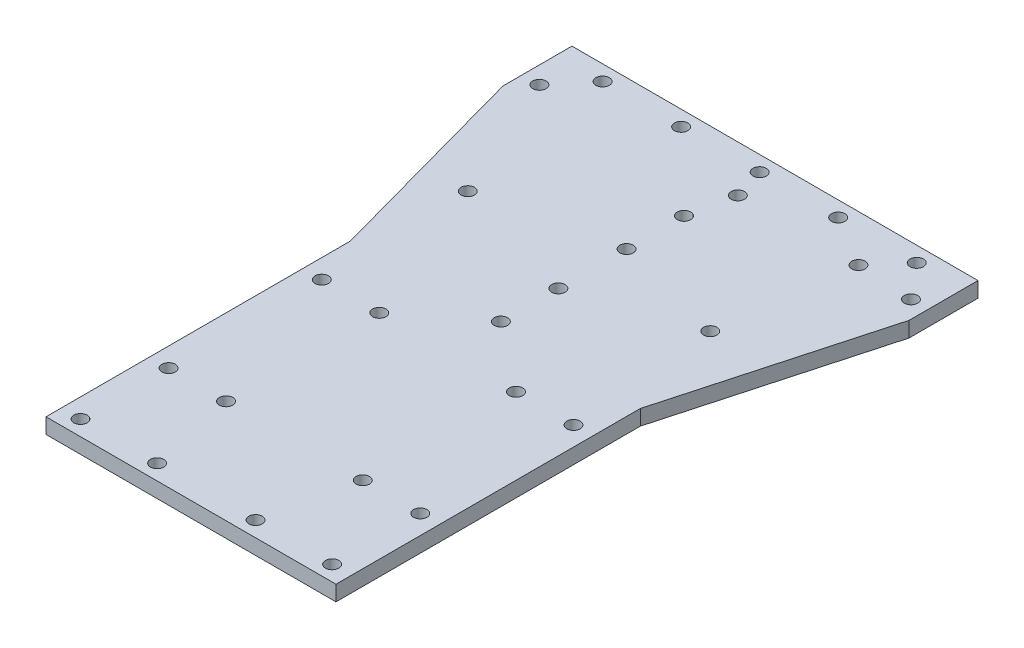
SolidWorks part; units mm, degrees
ref_plane "Front Plane" through (0, 0, 0) normal (0, 0, 1) x (1, 0, 0)
ref_plane "Top Plane" through (0, 0, 0) normal (0, 1, 0) x (1, 0, 0)
ref_plane "Right Plane" through (0, 0, 0) normal (1, 0, 0) x (0, 0, -1)
sketch "Sketch1" plane through (0, 0, 0) normal (0, 1, 0) x (1, 0, 0)
  line L1 (-37.85, 21.35) -> (37.85, 21.35)
  line L2 (-37.85, 21.35) -> (-37.85, -21.35)
  line L3 (-37.85, -21.35) -> (37.85, -21.35)
  line L4 (37.85, 21.35) -> (37.85, -21.35)
  line L5 (-37.85, 21.35) -> (37.85, -21.35) construction
  line L6 (-37.85, -21.35) -> (37.85, 21.35) construction
  circle A0 centre (2.4, 17.25) radius 1.75
  circle A1 centre (-33.8, -17.05) radius 1.75
  circle A2 centre (29.5, -17.05) radius 1.75
  circle A3 centre (33.9, 17.25) radius 1.75
  point P0 (0, 0)
  dimension "D9" = 3.5
  dimension "D1" = 75.7
  dimension "D2" = 42.7
  dimension "D3" = 4.1
  dimension "D4" = 4.3
  dimension "D5" = 4.05
  dimension "D6" = 8.35
  dimension "D7" = 3.95
  dimension "D8" = 40.25
extrude "Boss-Extrude1" add sketch "Sketch1" along normal blind 4
sketch "Sketch3" plane through (0, 4, 0) normal (0, 1, 0) x (1, 0, 0)
  line L0 (0, 0) -> (-31.55, 0) construction
  line L1 (-2.2, 0) -> (2.2, 0) construction
  line L2 (-31.55, 0) -> (-31.55, 14.5) construction
  line L3 (-31.55, 14.5) -> (27.25, 14.5) construction
  line L4 (27.25, 14.5) -> (27.25, -51.1) construction
  line L5 (27.25, -51.1) -> (-31.55, -51.1) construction
  line L6 (-31.55, -51.1) -> (-31.55, 0) construction
  line L7 (0, 14.5) -> (0, -51.1) construction
  line L8 (0, -2.2) -> (0, 2.2) construction
  line L9 (-31.55, -18.3) -> (27.25, -18.3) construction
  line L10 (-37.85, -21.35) -> (-37.85, -51.1)
  line L11 (37.85, -21.35) -> (37.85, -51.1)
  line L12 (37.85, -51.1) -> (-37.85, -51.1)
  line L13 (-37.85, -21.35) -> (37.85, -21.35)
  circle A0 centre (0, 5.6) radius 1.75
  circle A1 centre (0, -9.4) radius 1.75
  circle A2 centre (0, -27.2) radius 1.75
  circle A3 centre (0, -42.2) radius 1.75
  line M18 (-37.85, -21.35) -> (37.85, -21.35)
  dimension "D10" = 3.5
  dimension "D1" = 58.8
  dimension "D2" = 31.55
  dimension "D3" = 65.6
  dimension "D4" = 14.5
  dimension "D5" = 32.8
  dimension "D6" = 15
  dimension "D7" = 15
  dimension "D8" = 8.9
  dimension "D9" = 8.9
extrude "Boss-Extrude2" add sketch "Sketch3" against normal blind 4 contours L12 L11 L10 A3 A2 M18 region at (0, 4, 36.2381)
extrude "Cut-Extrude1" cut sketch "Sketch3<3>" against normal blind 4 contours A0 | A1
sketch "Sketch3<3>" plane through (0, 4, 0) normal (0, 1, 0) x (1, 0, 0) same geometry as "Sketch3"
sketch "Sketch4" plane through (0, 0, 0) normal (0, 1, 0) x (1, 0, 0)
  line L0 (-37.85, -51.1) -> (-37.85, -101.1) construction
  line L1 (-37.85, -101.1) -> (37.85, -101.1) construction
  line L2 (37.85, 21.35) -> (44, 21.35) construction
  line L3 (44, 21.35) -> (44, 29.35) construction
  line L4 (-37.85, 21.35) -> (-44, 21.35) construction
  line L6 (37.85, -51.1) -> (37.85, -101.1) construction
  line L7 (-44, 21.35) -> (-44, 29.35) construction
  line L8 (-44, 29.35) -> (44, 29.35) construction
  line L10 (-37.85, -51.1) -> (-37.85, -101.1)
  line L11 (-37.85, -101.1) -> (37.85, -101.1)
  line L12 (37.85, -101.1) -> (37.85, -51.1)
  line L13 (37.85, -51.1) -> (-37.85, -51.1)
  line L14 (-37.85, 21.35) -> (-44, 21.35)
  line L15 (-44, 21.35) -> (-44, 29.35)
  line L16 (-44, 29.35) -> (44, 29.35)
  line L17 (44, 29.35) -> (44, 21.35)
  line L18 (44, 21.35) -> (37.85, 21.35)
  line L19 (37.85, 21.35) -> (-37.85, 21.35)
  line L20 (0, -2.2) -> (0, 2.2) construction
  circle A0 centre (-32.85, -56.1) radius 1.75
  circle A1 centre (-17.85, -56.1) radius 1.75
  circle A2 centre (-17.85, -96.1) radius 1.75
  circle A3 centre (-32.85, -96.1) radius 1.75
  circle A4 centre (32.85, -96.1) radius 1.75
  circle A5 centre (17.85, -96.1) radius 1.75
  circle A6 centre (17.85, -56.1) radius 1.75
  circle A7 centre (32.85, -56.1) radius 1.75
  dimension "D5" = 3.5
  dimension "D1" = 88
  dimension "D2" = 8
  dimension "D3" = 50
  dimension "D4" = 6.15
  dimension "D6" = 15
  dimension "D7" = 5
  dimension "D8" = 5
  dimension "D9" = 5
extrude "Boss-Extrude3" add sketch "Sketch4" along normal blind 4
sketch "Sketch6" plane through (0, 4, 0) normal (0, 1, 0) x (1, 0, 0)
  line L0 (-44, 25.35) -> (44, 25.35) construction
  line L1 (-44, 29.35) -> (-44, 21.35) construction
  line L2 (44, 21.35) -> (44, 29.35) construction
  line L3 (-44, 29.35) -> (-53, 29.35)
  line L4 (-53, 29.35) -> (-53, 21.35)
  line L5 (-53, 21.35) -> (-44, 21.35)
  line L6 (44, 29.35) -> (53, 29.35)
  line L7 (53, 29.35) -> (53, 21.35)
  line L8 (53, 21.35) -> (44, 21.35)
  line L9 (44, 21.35) -> (44, 26.2514)
  line L10 (44, 29.35) -> (44, 26.2514)
  line L11 (-44, 21.35) -> (-44, 26.2514)
  line L12 (-44, 29.35) -> (-44, 26.2514)
  circle A0 centre (0, 25.35) radius 1.75
  circle A1 centre (20.5, 25.35) radius 1.75
  circle A2 centre (41, 25.35) radius 1.75
  circle A3 centre (-20.5, 25.35) radius 1.75
  circle A4 centre (-41, 25.35) radius 1.75
  point P29 (-44, 26.1589)
  point P30 (0, 0)
  point P31 (0, 0)
  point P34 (0, 0)
  point P35 (0, 0)
  point P36 (44, 26.0344)
  line M16 (44, 21.35) -> (44, 29.35)
  line M18 (-44, 29.35) -> (-44, 21.35)
  dimension "D5" = 3.5
  dimension "D1" = 20.5
  dimension "D2" = 20.5
  dimension "D3" = 20.5
  dimension "D4" = 20.5
  dimension "D6" = 12
  dimension "D7" = 12
extrude "Boss-Extrude4" add sketch "Sketch6" against normal blind 4 contours A4 L3 L4 L5 M18 | A2 L8 L7 L6 M16 region at (-48.5, 4, -25.35) region at (48.5, 4, -25.35)
extrude "Cut-Extrude2" cut sketch "Sketch6<3>" against normal through all contours A4 | A3 | A1 | A2 | A0
sketch "Sketch6<3>" plane through (0, 4, 0) normal (0, 1, 0) x (1, 0, 0) same geometry as "Sketch6"
sketch "Sketch7" plane through (0, 0, 0) normal (0, 1, 0) x (1, 0, 0)
  line L0 (-53, 21.35) -> (-53, 11.35)
  line L1 (-53, 11.35) -> (-37.85, 11.35)
  line L2 (-37.85, 21.35) -> (-37.85, -101.1) construction
  line L3 (-37.85, 11.35) -> (-37.85, 21.35)
  line L4 (-37.85, 21.35) -> (-53, 21.35)
  line L5 (53, 21.35) -> (53, 11.35)
  line L6 (53, 11.35) -> (37.85, 11.35)
  line L7 (37.85, -101.1) -> (37.85, 21.35) construction
  line L8 (37.85, 11.35) -> (37.85, 21.35)
  line L9 (37.85, 21.35) -> (53, 21.35)
  circle A0 centre (-48.5, 16.35) radius 1.75
  circle A1 centre (48.5, 16.35) radius 1.75
  dimension "D6" = 3.5
  dimension "D1" = 10
  dimension "D2" = 10
  dimension "D3" = 4.5
  dimension "D4" = 4.5
  dimension "D5" = 5
extrude "Boss-Extrude5" add sketch "Sketch7" along normal blind 4
sketch "Sketch8" plane through (0, 0, 0) normal (0, 1, 0) x (1, 0, 0)
  line L0 (-37.85, -101.1) -> (-37.85, -123.1)
  line L1 (-37.85, -123.1) -> (37.85, -123.1)
  line L2 (37.85, -123.1) -> (37.85, -101.1)
  line L3 (-37.85, -101.1) -> (37.85, -101.1)
  dimension "D1" = 22
extrude "Boss-Extrude6" add sketch "Sketch8" along normal blind 4
sketch "Sketch9" plane through (0, 4, 0) normal (0, 1, 0) x (1, 0, 0)
  line L0 (-37.85, -123.1) -> (-7.85, -123.1) construction
  line L1 (-37.85, -123.1) -> (37.85, -123.1) construction
  line L2 (-7.85, -123.1) -> (-7.85, -103.1) construction
  line L3 (-7.85, -103.1) -> (-37.85, -103.1) construction
  line L4 (-37.85, 11.35) -> (-37.85, -123.1) construction
  line L5 (-37.85, -103.1) -> (-37.85, -123.1) construction
  circle A2 centre (-12.85, -119.1) radius 1.75
  circle A3 centre (-32.85, -119.1) radius 1.75
  circle A4 centre (-32.85, -96.1) radius 1.75 construction
  dimension "D7" = 3.5
  dimension "D1" = 23
  dimension "D2" = 30
  dimension "D3" = 5
  dimension "D4" = 5
extrude "Cut-Extrude3" cut sketch "Sketch9" against normal through all
mirror "Mirror1" about plane through (0, 0, 0) normal (1, 0, 0) of "Cut-Extrude3"
sketch "Sketch10" plane through (0, 4, 0) normal (0, 1, 0) x (1, 0, 0)
  line L0 (-53, 11.35) -> (-37.85, -43.65)
  line L1 (-37.85, 11.35) -> (-37.85, -123.1) construction
  line L2 (53, 11.35) -> (37.85, -43.65)
  line L3 (37.85, -123.1) -> (37.85, 11.35) construction
  line L4 (37.85, -43.65) -> (37.85, 11.35)
  line L5 (37.85, 11.35) -> (53, 11.35)
  line L6 (-53, 11.35) -> (-37.85, 11.35)
  line L7 (-37.85, 11.35) -> (-37.85, -43.65)
  dimension "D1" = 55
  dimension "D2" = 55
extrude "Boss-Extrude7" add sketch "Sketch10" against normal blind 4
sketch "Sketch11" plane through (0, 4, 0) normal (0, 1, 0) x (1, 0, 0)
  line L0 (-35, 11.35) -> (-10, 11.35)
  line L1 (-10, 11.35) -> (-10, -48.65)
  line L2 (-10, -48.65) -> (-35, 11.35)
  line L3 (10, 11.35) -> (35, 11.35)
  line L4 (35, 11.35) -> (10, -48.65)
  line L5 (10, -48.65) -> (10, 11.35)
  line L6 (-10, 11.35) -> (0, 11.35) construction
  line L7 (0, -2.2) -> (0, 2.2) construction
  line L8 (0, 11.35) -> (10, 11.35) construction
  dimension "D1" = 60
  dimension "D2" = 10
  dimension "D3" = 25
